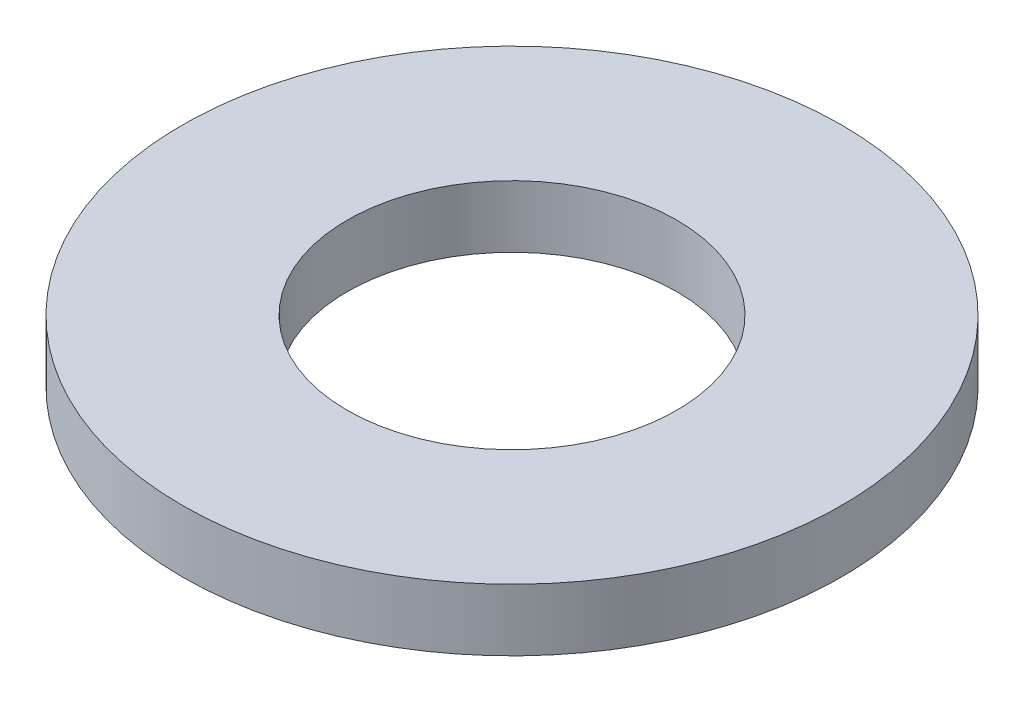
SolidWorks part; units mm, degrees
ref_plane "Front Plane" through (0, 0, 0) normal (0, 0, 1) x (1, 0, 0)
ref_plane "Top Plane" through (0, 0, 0) normal (0, 1, 0) x (1, 0, 0)
ref_plane "Right Plane" through (0, 0, 0) normal (1, 0, 0) x (0, 0, -1)
sketch "Sketch1" plane through (0, 0, 0) normal (0, 1, 0) x (1, 0, 0)
  circle A0 centre (0, 0) radius 85
  dimension "FLANGE_OD" = 170
extrude "Boss-Extrude1" add sketch "Sketch1" along normal blind 16
sketch "Sketch2" plane through (0, 0, 0) normal (0, 1, 0) x (1, 0, 0)
  circle A0 centre (0, 0) radius 42.5
  dimension "BORE_D" = 85
extrude "Cut-Extrude1" cut sketch "Sketch2" along normal through all
sketch "Sketch3" plane through (0, 16, 0) normal (0, 1, 0) x (1, 0, 0)
  circle A0 centre (0, 0) radius 29.0301 construction
  circle A1 centre (-29.0301, 0) radius 6.4931
  dimension "BOLT_D" = 12.9863
  dimension "BOLT_PCD" = 58.0603
extrude "Cut-Extrude2" cut sketch "Sketch3" against normal blind 9.8879 rebuild error yes
pattern_circular "CirPattern1" count 5 over 360 rebuild error yes
